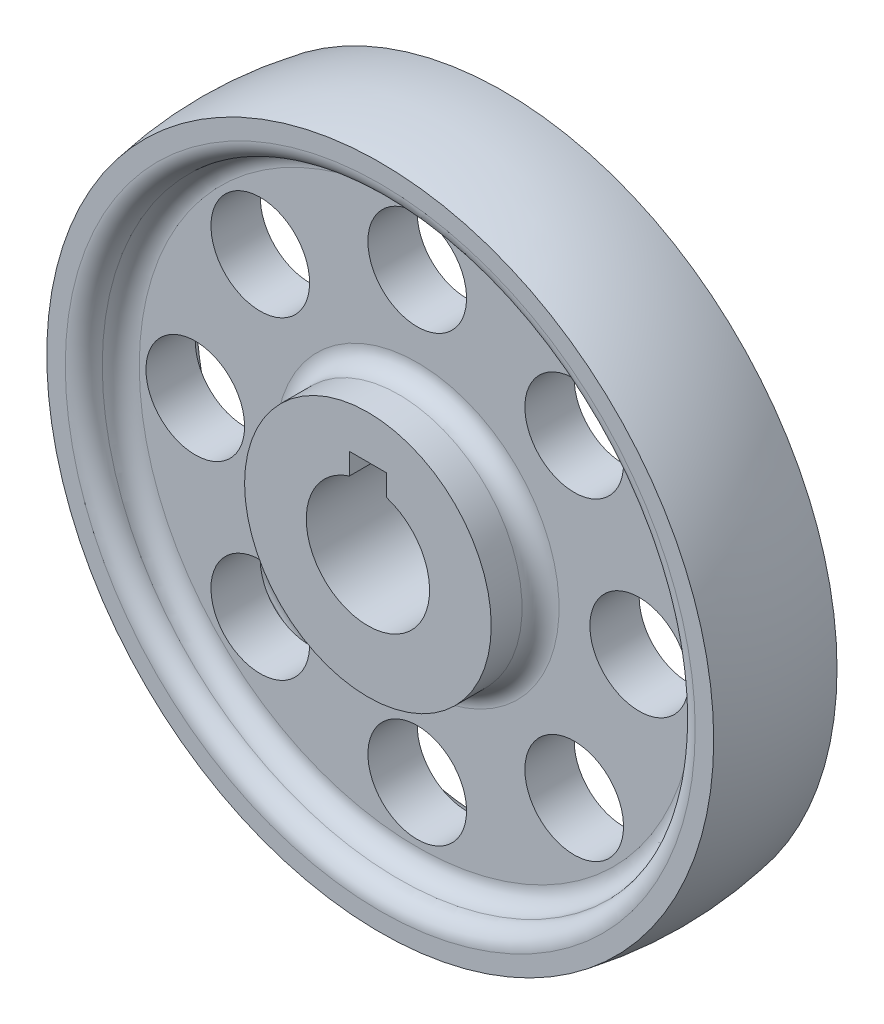
SolidWorks part; units mm, degrees
ref_plane "Front Plane" through (0, 0, 0) normal (0, 0, 1) x (1, 0, 0)
ref_plane "Top Plane" through (0, 0, 0) normal (0, 1, 0) x (1, 0, 0)
ref_plane "Right Plane" through (0, 0, 0) normal (1, 0, 0) x (0, 0, -1)
sketch "Sketch1" plane through (0, 0, 0) normal (0, 0, 1) x (1, 0, 0)
  circle A0 centre (0, 0) radius 20
  dimension "D1" = 40
extrude "Extrude1" add sketch "Sketch1" along normal blind 16
sketch "Sketch2" plane through (0, 0, 0) normal (0, 0, -1) x (-1, 0, 0)
  circle A0 centre (0, 0) radius 15
  dimension "D1" = 30
extrude "Extrude2" add sketch "Sketch2" along normal blind 8
sketch "Sketch3" plane through (0, 0, -8) normal (0, 0, -1) x (-1, 0, 0)
  circle A0 centre (0, 0) radius 10
  dimension "D1" = 20
extrude "Cut-Extrude1" cut sketch "Sketch3" against normal through all
sketch "Sketch4" plane through (0, 0, -8) normal (0, 0, -1) x (-1, 0, 0)
  line L1 (-3, 8.7202) -> (3, 8.7202)
  line L2 (-3, 8.7202) -> (-3, 13)
  line L3 (-3, 13) -> (3, 13)
  line L4 (3, 8.7202) -> (3, 13)
  circle A6 centre (0, 0) radius 10 construction
  dimension "D1" = 6
  dimension "D2" = 3
  dimension "D3" = 23
extrude "Cut-Extrude2" cut sketch "Sketch4" against normal through all
fillet "Fillet1" radius 3 1 edges at (15, 0, 0)
sketch "Sketch5" plane through (0, 0, 0) normal (0, 1, 0) x (1, 0, 0)
  line L0 (0, -8) -> (48.0833, -8)
  line L1 (-20, -16) -> (20, -16) construction
  line L2 (48.0833, -8) -> (48.0833, -14)
  line L3 (48.0833, -14) -> (54.0833, -14)
  line L5 (48.0833, 0) -> (0, 0)
  line L6 (0, 0) -> (0, -8)
  line L7 (0, -16) -> (0, 0) construction
  line L8 (54.0833, 6) -> (48.0833, 6)
  line L9 (48.0833, 6) -> (48.0833, 0)
  arc A0 (54.0833, 6) -> (54.0833, -14) centre (0, -4) cw
  dimension "D4" = 6
  dimension "D8" = 55
  dimension "D1" = 8
  dimension "D3" = 6
  dimension "D5" = 6
  dimension "D6" = 8
  dimension "D7" = 6
revolve "Revolve1" add sketch "Sketch5" angle 360 about L6
fillet "Fillet3" radius 3 2 edges at (-48.0833, 0, -6) (-48.0833, 0, 0)
fillet "Fillet4" radius 3 2 edges at (-48.0833, 0, 14) (-48.0833, 0, 8)
sketch "Sketch6" plane through (0, 0, 0) normal (0, 0, -1) x (-1, 0, 0)
  circle A0 centre (0, 36) radius 8
  dimension "D2" = 16
  dimension "D1" = 36
extrude "Cut-Extrude3" cut sketch "Sketch6" against normal through all
pattern_circular "CirPattern1" count 8 over 360 about axis through (0, 0, -8) along (0, 0, 1) of "Cut-Extrude3"
sketch "Sketch7" plane through (0, 0, 0) normal (0, 0, -1) x (-1, 0, 0)
  line L0 (3, 9.5394) -> (3, 13)
  line L1 (3, 13) -> (-3, 13)
  line L2 (-3, 13) -> (-3, 9.5394)
  arc A0 (-3, 9.5394) -> (3, 9.5394) centre (0, 0) ccw
extrude "Cut-Extrude4" cut sketch "Sketch7" against normal through all
fillet "Fillet5" radius 3 1 edges at (-20, 0, 8)
